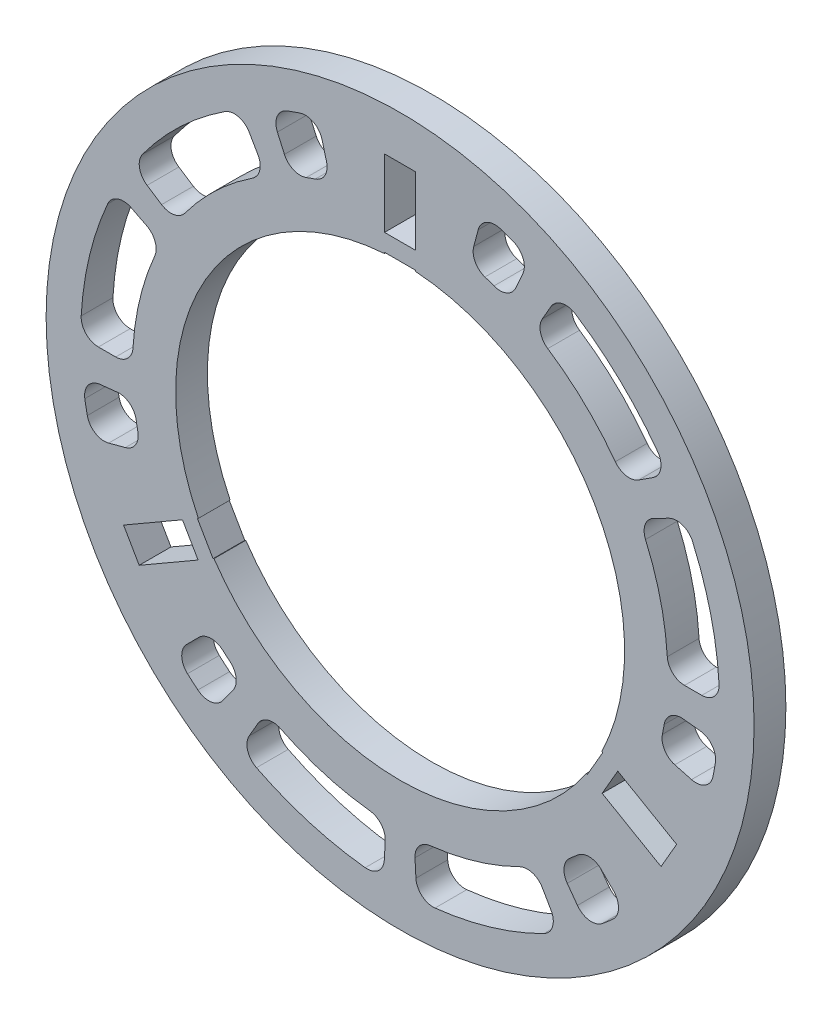
SolidWorks part; units mm, degrees
ref_plane "Front Plane" through (0, 0, 0) normal (0, 0, 1) x (1, 0, 0)
ref_plane "Top Plane" through (0, 0, 0) normal (0, 1, 0) x (1, 0, 0)
ref_plane "Right Plane" through (0, 0, 0) normal (1, 0, 0) x (0, 0, -1)
sketch "Sketch1" plane through (0, 0, 0) normal (0, 0, 1) x (1, 0, 0)
  line L0 (0, 0) -> (0, 50.8) construction
  line L1 (47.9712, -31.0114) -> (50.8422, -26.0386)
  line L2 (2.871, 57.05) -> (-2.871, 57.05)
  line L3 (2.871, 57.05) -> (2.871, 44.55)
  line L4 (2.871, 44.55) -> (-2.871, 44.55)
  line L5 (-2.871, 57.05) -> (-2.871, 44.55)
  line L6 (2.871, 57.05) -> (-2.871, 44.55) construction
  line L7 (2.871, 44.55) -> (-2.871, 57.05) construction
  line L8 (47.9712, -31.0114) -> (37.1459, -24.7614)
  line L9 (37.1459, -24.7614) -> (40.0169, -19.7886)
  line L10 (50.8422, -26.0386) -> (40.0169, -19.7886)
  line L11 (47.9712, -31.0114) -> (40.0169, -19.7886) construction
  line L12 (37.1459, -24.7614) -> (50.8422, -26.0386) construction
  line L13 (-50.8422, -26.0386) -> (-47.9712, -31.0114)
  line L14 (-50.8422, -26.0386) -> (-40.0169, -19.7886)
  line L15 (-40.0169, -19.7886) -> (-37.1459, -24.7614)
  line L16 (-47.9712, -31.0114) -> (-37.1459, -24.7614)
  line L17 (-50.8422, -26.0386) -> (-37.1459, -24.7614) construction
  line L18 (-40.0169, -19.7886) -> (-47.9712, -31.0114) construction
  line L19 (-2.871, 41.375) -> (2.871, 41.375)
  line L20 (-2.871, 41.175) -> (-2.871, 41.375)
  line L21 (2.871, 41.175) -> (2.871, 41.375)
  line L22 (34.2231, -23.0739) -> (34.3963, -23.1739)
  line L23 (37.2673, -18.2011) -> (34.3963, -23.1739)
  line L24 (37.0941, -18.1012) -> (37.2673, -18.2011)
  line L25 (-37.0941, -18.1012) -> (-37.2673, -18.2011)
  line L26 (-34.3963, -23.1739) -> (-37.2673, -18.2011)
  line L27 (0, 0) -> (32.5438, 56.3674) construction
  line L28 (-34.2231, -23.0739) -> (-34.3963, -23.1739)
  arc A0 (-2.871, 41.175) -> (-37.0941, -18.1012) centre (0, 0) ccw
  circle A1 centre (0, 0) radius 65.0875
  circle A2 centre (0, 0) radius 50.8 construction
  arc A3 (37.0941, -18.1012) -> (2.871, 41.175) centre (0, 0) ccw
  arc A4 (-34.2231, -23.0739) -> (34.2231, -23.0739) centre (0, 0) ccw
  point P21 (0, 0)
  point P32 (0, 0)
  point P34 (0, 0)
  dimension "D1" = 82.55
  dimension "D2" = 130.175
  dimension "D8" = 3.175
  dimension "D10" = 101.6
  dimension "D3" = 50.8
  dimension "D4" = 12.5
  dimension "D5" = 5.742
  dimension "D7" = 30
  dimension "D6" = 3
  dimension "D9" = 3
extrude "Boss-Extrude1" add sketch "Sketch1" along normal blind 5.842
sketch "Sketch3" plane through (0, 0, 5.842) normal (0, 0, 1) x (1, 0, 0)
  line L0 (0, 0) -> (0, 65.0875) construction
  line L1 (0, 0) -> (-56.3674, 32.5437) construction
  line L2 (-24.6063, 42.6193) -> (-29.3688, 50.8682)
  line L3 (-49.2125, 0) -> (-58.7375, 0)
  line L4 (-41.2731, 26.803) -> (-49.2614, 31.9907)
  line L5 (-43.8487, 22.342) -> (-52.3355, 26.6663)
  line L6 (43.8487, 22.342) -> (52.3355, 26.6663)
  line L7 (41.2731, 26.803) -> (49.2614, 31.9907)
  line L8 (24.6063, 42.6193) -> (29.3688, 50.8682)
  line L9 (49.2125, 0) -> (58.7375, 0)
  line L10 (-2.5756, -49.1451) -> (-3.0741, -58.657)
  line L11 (2.5756, -49.1451) -> (3.0741, -58.657)
  line L12 (24.6062, -42.6193) -> (29.3687, -50.8682)
  line L13 (-24.6063, -42.6193) -> (-29.3688, -50.8682)
  line L14 (-20.0165, 44.9579) -> (-23.8907, 53.6594)
  line L15 (-15.2024, 56.7361) -> (-12.7371, 47.5356)
  line L16 (-56.7361, -15.2024) -> (-47.5356, -12.7371)
  line L17 (-48.9429, -5.1441) -> (-58.4157, -6.1397)
  line L18 (48.9429, -5.1441) -> (58.4157, -6.1397)
  line L19 (56.7361, -15.2024) -> (47.5356, -12.7371)
  line L20 (15.2024, 56.7361) -> (12.7371, 47.5356)
  line L21 (20.0165, 44.9579) -> (23.8907, 53.6594)
  line L22 (-28.9264, -39.8137) -> (-34.525, -47.5196)
  line L23 (-41.5337, -41.5337) -> (-34.7985, -34.7985)
  line L24 (41.5337, -41.5337) -> (34.7985, -34.7985)
  line L25 (28.9264, -39.8137) -> (34.525, -47.5196)
  circle A0 centre (0, 0) radius 65.0875 construction
  arc A1 (-29.3688, 50.8682) -> (-49.2614, 31.9907) centre (0, 0) ccw
  arc A2 (-24.6063, 42.6193) -> (-41.2731, 26.803) centre (0, 0) ccw
  arc A3 (-43.8487, 22.342) -> (-49.2125, 0) centre (0, 0) ccw
  circle A4 centre (0, 0) radius 49.2125 construction
  circle A5 centre (0, 0) radius 58.7375 construction
  arc A6 (-52.3355, 26.6663) -> (-58.7375, 0) centre (0, 0) ccw
  arc A7 (58.7375, 0) -> (52.3355, 26.6663) centre (0, 0) ccw
  arc A8 (49.2614, 31.9907) -> (29.3688, 50.8682) centre (0, 0) ccw
  arc A9 (41.2731, 26.803) -> (24.6063, 42.6193) centre (0, 0) ccw
  arc A10 (49.2125, 0) -> (43.8487, 22.342) centre (0, 0) ccw
  arc A11 (-29.3688, -50.8682) -> (-3.0741, -58.657) centre (0, 0) ccw
  arc A12 (3.0741, -58.657) -> (29.3687, -50.8682) centre (0, 0) ccw
  arc A13 (2.5756, -49.1451) -> (24.6062, -42.6193) centre (0, 0) ccw
  arc A14 (-24.6063, -42.6193) -> (-2.5756, -49.1451) centre (0, 0) ccw
  arc A15 (-24.6063, 42.6193) -> (-41.2731, 26.803) centre (0, 0) ccw
  arc A16 (-29.3688, 50.8682) -> (-49.2614, 31.9907) centre (0, 0) ccw
  arc A17 (-43.8487, 22.342) -> (-49.2125, 0) centre (0, 0) ccw
  arc A18 (-52.3355, 26.6663) -> (-58.7375, 0) centre (0, 0) ccw
  arc A19 (-24.6063, -42.6193) -> (-2.5756, -49.1451) centre (0, 0) ccw
  arc A20 (-29.3688, -50.8682) -> (-3.0741, -58.657) centre (0, 0) ccw
  arc A21 (2.5756, -49.1451) -> (24.6062, -42.6193) centre (0, 0) ccw
  arc A22 (3.0741, -58.657) -> (29.3687, -50.8682) centre (0, 0) ccw
  arc A23 (58.7375, 0) -> (52.3355, 26.6663) centre (0, 0) ccw
  arc A24 (49.2125, 0) -> (43.8487, 22.342) centre (0, 0) ccw
  arc A25 (41.2731, 26.803) -> (24.6063, 42.6193) centre (0, 0) ccw
  arc A26 (49.2614, 31.9907) -> (29.3688, 50.8682) centre (0, 0) ccw
  arc A27 (-12.7371, 47.5356) -> (-20.0165, 44.9579) centre (0, 0) ccw
  arc A28 (-15.2024, 56.7361) -> (-23.8907, 53.6594) centre (0, 0) ccw
  arc A29 (-56.7361, -15.2024) -> (-58.4157, -6.1397) centre (0, 0) cw
  arc A30 (-47.5356, -12.7371) -> (-48.9429, -5.1441) centre (0, 0) cw
  arc A31 (56.7361, -15.2024) -> (58.4157, -6.1397) centre (0, 0) ccw
  arc A32 (47.5356, -12.7371) -> (48.9429, -5.1441) centre (0, 0) ccw
  arc A33 (15.2024, 56.7361) -> (23.8907, 53.6594) centre (0, 0) cw
  arc A34 (12.7371, 47.5356) -> (20.0165, 44.9579) centre (0, 0) cw
  arc A35 (-41.5337, -41.5337) -> (-34.525, -47.5196) centre (0, 0) ccw
  arc A36 (-34.7985, -34.7985) -> (-28.9264, -39.8137) centre (0, 0) ccw
  arc A37 (41.5337, -41.5337) -> (34.525, -47.5196) centre (0, 0) cw
  arc A38 (34.7985, -34.7985) -> (28.9264, -39.8137) centre (0, 0) cw
  point P8 (56.171, 17.1732)
  point P13 (49.2125, 0)
  point P38 (0, 0)
  point P63 (0, 0)
  dimension "D2" = 117.475
  dimension "D1" = 60
  dimension "D4" = 30
  dimension "D5" = 3
  dimension "D7" = 36
  dimension "D8" = 45
  dimension "D3" = 9.525
  dimension "D6" = 3
  dimension "D9" = 3
extrude "Cut-Extrude2" cut sketch "Sketch3" against normal through all contours A2 L2 A1 L4 | L5 A6 L3 A3 | L16 A30 L17 A29 | L15 A28 L14 A27 | L20 A34 L21 A33 | A9 L7 A8 L8 | A10 L9 A7 L6 | A32 L19 A31 L18 | L24 A38 L25 A37 | A13 L11 A12 L12 | A14 L13 A11 L10 | A36 L23 A35 L22 region at (-36.9066, 38.8915, 5.842) region at (-52.1343, 12.5163, 5.842) region at (52.1343, 12.5163, 5.842) region at (36.9066, 38.8915, 5.842) region at (-15.2277, -51.4078, 5.842) region at (15.2277, -51.4078, 5.842) region at (-18.0454, 50.9587, 5.842) region at (-53.1542, -9.8516, 5.842) region at (53.1542, -9.8516, 5.842) region at (18.0454, 50.9587, 5.842) region at (-35.1088, -41.1071, 5.842) region at (35.1088, -41.1071, 5.842)
fillet "Fillet1" radius 3.175 48 edges at (-52.3355, 26.6663, 2.921) (-58.4157, -6.1397, 2.921) (-43.8487, 22.342, 2.921) (-48.9429, -5.1441, 2.921) (-58.7375, 0, 2.921) (-56.7361, -15.2024, 2.921) (-47.5356, -12.7371, 2.921) (-49.2125, 0, 2.921) (-41.2731, 26.803, 2.921) (-49.2614, 31.9907, 2.921) (-20.0165, 44.9579, 2.921) (-12.7371, 47.5356, 2.921) (-15.2024, 56.7361, 2.921) (-23.8907, 53.6594, 2.921) (-29.3688, 50.8682, 2.921) (-24.6063, 42.6193, 2.921) (41.5337, -41.5337, 2.921) (34.525, -47.5196, 2.921) (34.7985, -34.7985, 2.921) (28.9264, -39.8137, 2.921) (3.0741, -58.657, 2.921) (2.5756, -49.1451, 2.921) (24.6062, -42.6193, 2.921) (29.3687, -50.8682, 2.921) (-3.0741, -58.657, 2.921) (-2.5756, -49.1451, 2.921) (-29.3688, -50.8682, 2.921) (-24.6063, -42.6193, 2.921) (-28.9264, -39.8137, 2.921) (-41.5337, -41.5337, 2.921) (-34.7985, -34.7985, 2.921) (-34.525, -47.5196, 2.921) (48.9429, -5.1441, 2.921) (58.4157, -6.1397, 2.921) (56.7361, -15.2024, 2.921) (47.5356, -12.7371, 2.921) (58.7375, 0, 2.921) (49.2125, 0, 2.921) (52.3355, 26.6663, 2.921) (43.8487, 22.342, 2.921) (49.2614, 31.9907, 2.921) (41.2731, 26.803, 2.921) (29.3688, 50.8682, 2.921) (23.8907, 53.6594, 2.921) (15.2024, 56.7361, 2.921) (24.6063, 42.6193, 2.921) (12.7371, 47.5356, 2.921) (20.0165, 44.9579, 2.921)
